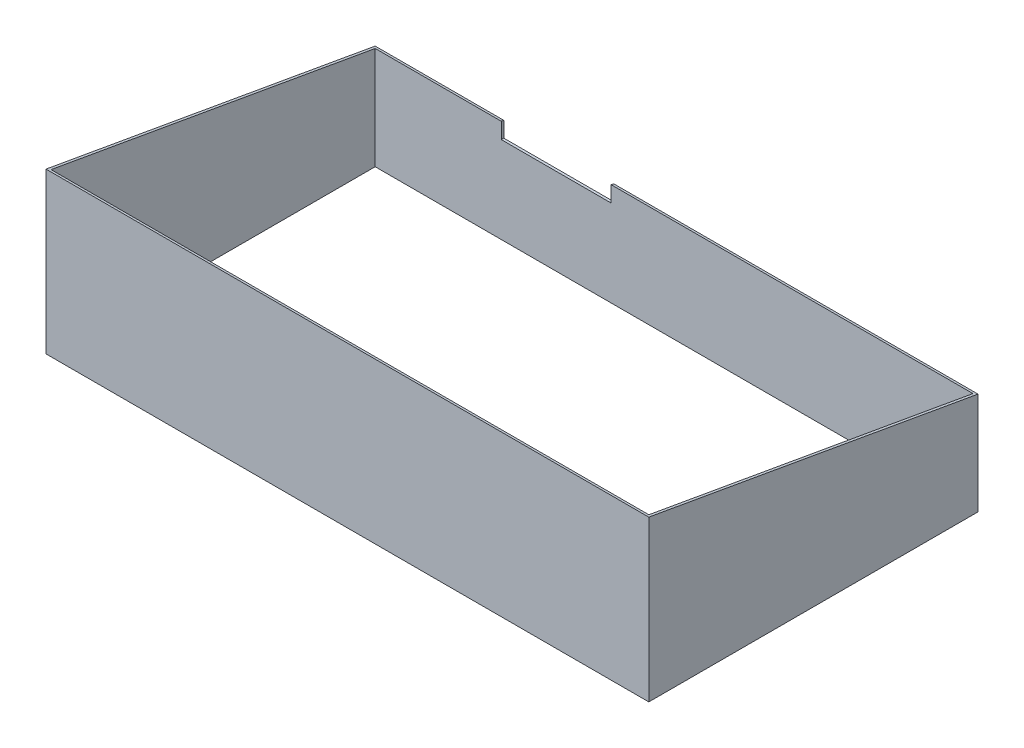
SolidWorks part; units mm, degrees
material "Particle Board"
ref_plane "Front Plane" through (0, 0, 0) normal (0, 0, 1) x (1, 0, 0)
ref_plane "Top Plane" through (0, 0, 0) normal (0, 1, 0) x (1, 0, 0)
ref_plane "Right Plane" through (0, 0, 0) normal (1, 0, 0) x (0, 0, -1)
sketch "Sketch1" plane through (0, 0, 0) normal (1, 0, 0) x (0, 0, -1)
  line L0 (0, 403.2291) -> (0, 0)
  line L1 (0, 0) -> (829.3066, 0)
  line L4 (829.3066, 0) -> (829.3066, 257)
  line L5 (0, 403.2291) -> (829.3066, 257)
  dimension "D1" = 10
  dimension "D2" = 842.1
  dimension "D3" = 257
extrude "Boss-Extrude1" add sketch "Sketch1" along normal blind 1518.68
shell "Shell1" thickness 6.35 removed face at (759.34, 0, -414.6533) removed face at (759.34, 330.1146, -414.6533)
sketch "Sketch3" plane through (0, 0, -822.9566) normal (0, 0, 1) x (1, 0, 0)
  line L0 (6.35, 0) -> (6.35, 258.1197) construction
  line L1 (324, 268.1197) -> (601, 268.1197)
  line L2 (324, 268.1197) -> (324, 218.1197)
  line L3 (324, 218.1197) -> (601, 218.1197)
  line L4 (601, 268.1197) -> (601, 218.1197)
  line L5 (1512.33, 258.1197) -> (6.35, 258.1197) construction
  dimension "D1" = 317.65
  dimension "D2" = 277
  dimension "D3" = 10
  dimension "D4" = 40
extrude "Cut-Extrude2" cut sketch "Sketch3" against normal up to next
